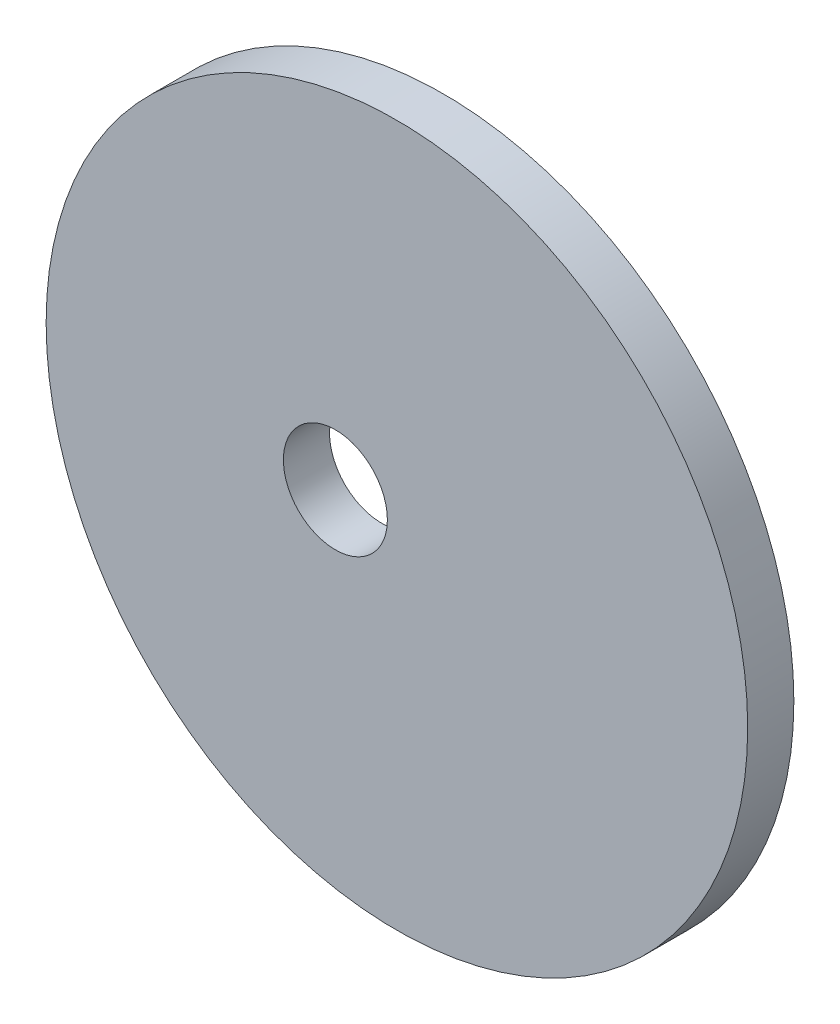
SolidWorks part; units mm, degrees
ref_plane "Front Plane" through (0, 0, 0) normal (0, 0, 1) x (1, 0, 0)
ref_plane "Top Plane" through (0, 0, 0) normal (0, 1, 0) x (1, 0, 0)
ref_plane "Right Plane" through (0, 0, 0) normal (1, 0, 0) x (0, 0, -1)
sketch "Sketch1" plane through (0, 0, 0) normal (0, 0, 1) x (1, 0, 0)
  circle A0 centre (0, 0) radius 22.8
  circle A2 centre (-4, 0) radius 3.38
extrude "Boss-Extrude5" add sketch "Sketch1" along normal blind 3 contours A2 | A0 region at (-4, 0, 0)
sketch "Sketch2" plane through (0, 0, 0) normal (0, 0, 1) x (1, 0, 0)
  circle A0 centre (0, 0) radius 23.75
sketch "Sketch3" plane through (0, 0, 0) normal (0, 0, 1) x (1, 0, 0)
  circle A0 centre (-4, 0) radius 3.175
